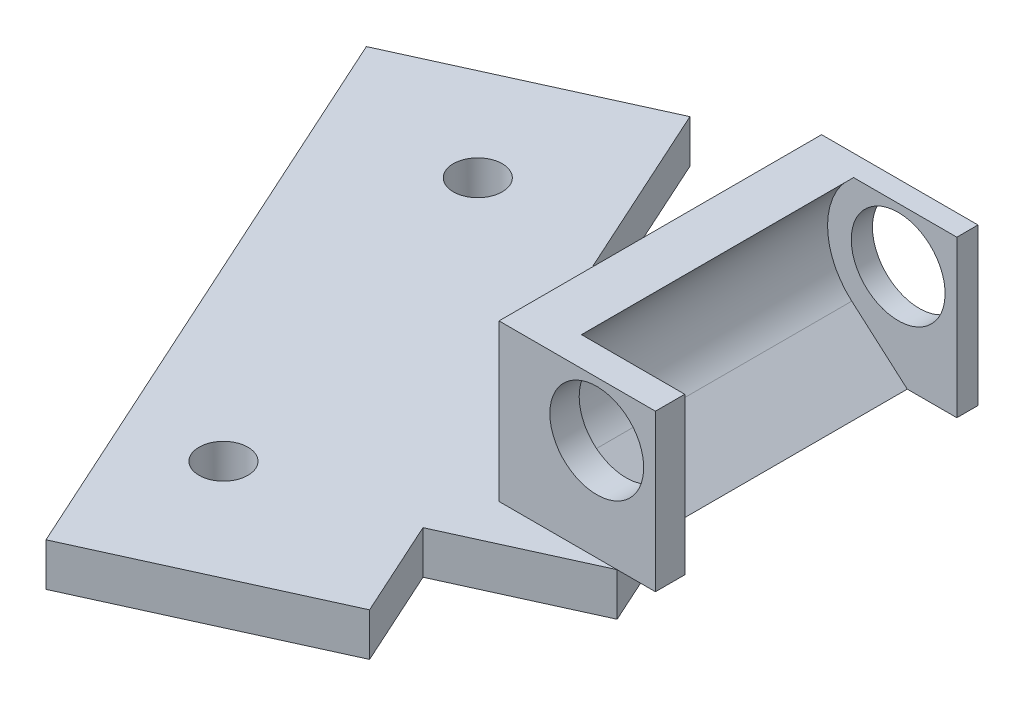
SolidWorks part; units mm, degrees
ref_plane "Front Plane" through (0, 0, 0) normal (0, 0, 1) x (1, 0, 0)
ref_plane "Top Plane" through (0, 0, 0) normal (0, 1, 0) x (1, 0, 0)
ref_plane "Right Plane" through (0, 0, 0) normal (1, 0, 0) x (0, 0, -1)
sketch "Sketch2" plane through (0, 0, 0) normal (0, 0, 1) x (1, 0, 0)
  line L0 (-516.8423, 96.792) -> (-496.5223, 96.792)
  line L1 (-496.5223, 96.792) -> (-496.5223, 117.112)
  line L2 (-496.5223, 117.112) -> (-516.8423, 117.112)
  line L3 (-516.8423, 117.112) -> (-516.8423, 96.792)
  line L4 (-487.9141, 83.661) -> (-510.1749, 103.0871) construction
  line L5 (-487.9141, 83.661) -> (-510.1749, 103.0871)
  circle A0 centre (-504.1423, 110) radius 6.096
  arc A1 (-500.0378, 118.2057) -> (-510.1749, 103.0871) centre (-504.1423, 110) ccw construction
  arc A2 (-500.0378, 118.2057) -> (-510.1749, 103.0871) centre (-504.1423, 110) ccw
  line M7 (-510.1749, 103.0871) -> (-487.9141, 83.661)
  arc M12 (-500.0378, 118.2057) -> (-510.1749, 103.0871) centre (-504.1423, 110) ccw
  dimension "D1" = 20.32
  dimension "D4" = 12.192
  dimension "D2" = 20.32
  dimension "D3" = 12.7
  dimension "D5" = 7.112
extrude "Boss-Extrude1" add sketch "Sketch2" against normal blind 38.1 contours L2 L3 L0 M7 M12 region at (-512.9744, 104.8078, 0)
sketch "Sketch5" plane through (0, 0, 0) normal (0, 0, 1) x (1, 0, 0)
  line L0 (-525.7847, 30.226) -> (321.5154, 30.226) construction
  line L1 (-516.8423, 96.792) -> (-496.5223, 96.792)
  line L2 (-516.8423, 96.792) -> (-516.8423, 117.112)
  line L3 (-516.8423, 117.112) -> (-496.5223, 117.112)
  line L4 (-496.5223, 96.792) -> (-496.5223, 117.112)
  circle A0 centre (-504.1423, 110) radius 6.096
  dimension "D1" = 20.32
  dimension "D3" = 12.192
  dimension "D2" = 20.32
extrude "Boss-Extrude2" add sketch "Sketch5" along normal blind 3.81
sketch "Sketch6" plane through (0, 0, -38.1) normal (0, 0, -1) x (-1, 0, 0)
  line L1 (516.8423, 96.792) -> (496.5223, 96.792)
  line L2 (516.8423, 96.792) -> (516.8423, 117.112)
  line L3 (516.8423, 117.112) -> (496.5223, 117.112)
  line L4 (496.5223, 96.792) -> (496.5223, 117.112)
  circle A0 centre (504.1423, 110) radius 6.096
  dimension "D1" = 12.192
extrude "Boss-Extrude3" add sketch "Sketch6" against normal up to surface (2.75 mm away)
sketch "Sketch7" plane through (0, 96.792, 0) normal (0, -1, 0) x (1, 0, 0)
  line L0 (-547.7435, -51.8962) -> (-576.6476, -38.7579)
  line L1 (-576.6476, -38.7579) -> (-541.9626, 37.549)
  line L2 (-541.9626, 37.549) -> (-513.0585, 24.4108)
  line L3 (-513.0585, 24.4108) -> (-518.8393, 11.6929)
  line L4 (-518.8393, 11.6929) -> (-501.4968, 3.81)
  line L5 (-496.5223, 3.81) -> (-516.8423, 3.81) construction
  line L6 (-547.7435, -51.8962) -> (-537.2329, -28.7728)
  line L7 (-537.2329, -28.7728) -> (-519.8904, -36.6558)
  line L8 (-519.8904, -36.6558) -> (-501.4968, 3.81)
  circle A0 centre (-554.6451, -31.2325) radius 3.175
  circle A1 centre (-539.2691, 17.1846) radius 3.175
  dimension "D7" = 6.35
  dimension "D8" = 6.35
  dimension "D2" = 13.97
  dimension "D3" = 31.75
  dimension "D4" = 83.82
  dimension "D5" = 19.05
  dimension "D6" = 6.35
  dimension "D9" = 25.4
  dimension "D10" = 13.97
  dimension "D11" = 19.05
extrude "Boss-Extrude5" add sketch "Sketch7" along normal up to surface (5.5806 mm away)
